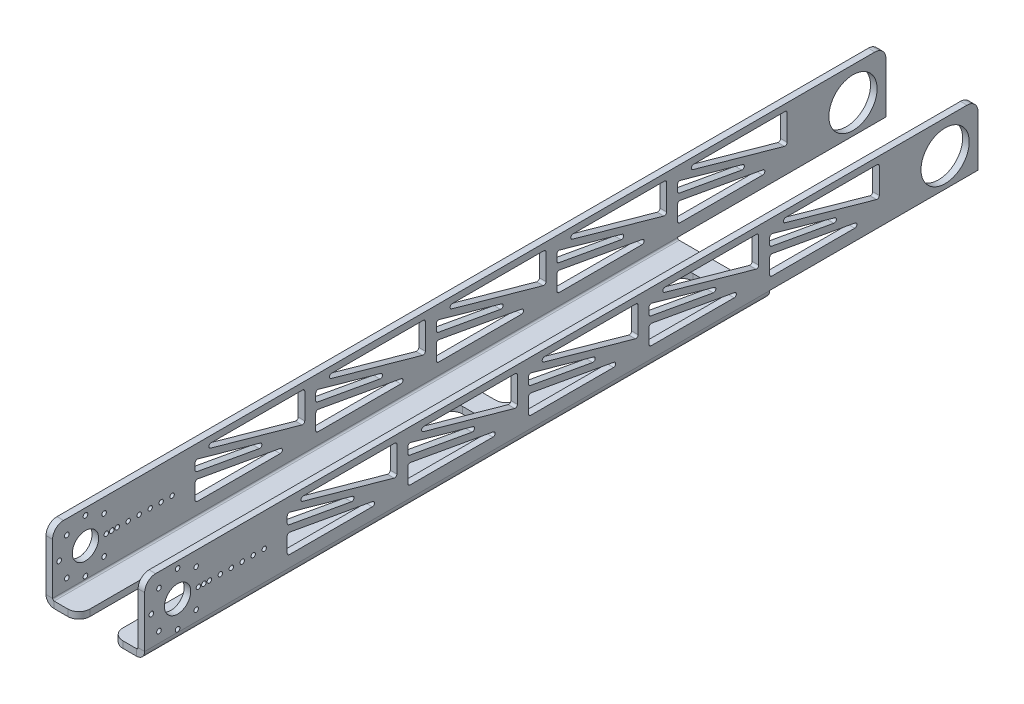
SolidWorks part; units mm, degrees
material "6061 Alloy"
ref_plane "Front Plane" through (0, 0, 0) normal (0, 0, 1) x (1, 0, 0)
ref_plane "Top Plane" through (0, 0, 0) normal (0, 1, 0) x (1, 0, 0)
ref_plane "Right Plane" through (0, 0, 0) normal (1, 0, 0) x (0, 0, -1)
sketch "Sketch1" plane through (0, 0, 0) normal (0, 1, 0) x (1, 0, 0)
  line L1 (-22.5, -190) -> (22.5, -190)
  line L2 (-22.5, -190) -> (-22.5, 190)
  line L3 (-22.5, 190) -> (22.5, 190)
  line L4 (22.5, -190) -> (22.5, 190)
  line L5 (0, 190) -> (0, -190) construction
  line L6 (-22.5, 0) -> (22.5, 0) construction
  point P0 (0, 0)
  dimension "D1" = 380
  dimension "D2" = 45
base flange "Base-Flange1" sketch "Sketch1" thickness 3 reverse thickness direction no parameters "D1"=0.7366
edge flange "Edge-Flange1" sketch "Sketch10" flange profiles "Sketch10", "Sketch11" flange angle 90 flange length 32 flange position material inside bend radius 0.7366 thickness 3 relief rectangular parameters "D6"=10, "D8"=1
sketch "Sketch10" plane through (-22.5, 0, 0) normal (-1, 0, 0) x (0, 0, 1)
  line L2 (-190, 0) -> (-190, 29)
  line L3 (-190, 29) -> (190, 29)
  line L4 (190, 29) -> (190, 0)
  line L7 (-190, 0) -> (190, 0) construction
  line L8 (-190, 0) -> (190, 0)
sketch "Sketch11" plane through (22.5, 0, 0) normal (1, 0, 0) x (0, 0, -1)
  line L2 (190, 0) -> (190, 29)
  line L3 (190, 29) -> (-190, 29)
  line L4 (-190, 29) -> (-190, 0)
  line L13 (-190, 0) -> (190, 0) construction
  line L14 (-190, 0) -> (190, 0)
bend "EdgeBend1" bend radius 0.7366 bend angle 90 parameters "D5"=1
bend "EdgeBend2" bend radius 0.7366 bend angle 90 parameters "D5"=2
sketch "Sketch12" plane through (0, 0, 0) normal (0, 1, 0) x (1, 0, 0)
  line L32 (7.5, -10) -> (-7.5, -10)
  line L33 (-7.5, -10) -> (-7.5, 85)
  line L34 (-7.5, 85) -> (7.5, 85)
  line L35 (7.5, -10) -> (7.5, 85)
  line L36 (7.5, -115) -> (-7.5, -115)
  line L37 (-7.5, -115) -> (-7.5, -20)
  line L38 (-7.5, -20) -> (7.5, -20)
  line L39 (7.5, -115) -> (7.5, -20)
  line L44 (-7.5, 85) -> (7.5, -10) construction
  point P6 (0, 37.5)
  dimension "D3" = 15
  dimension "D5" = 10
  dimension "D7" = 95
  dimension "D8" = 15
  dimension "D9" = 95
  dimension "D1" = 10
extrude "Cut-Extrude1" cut sketch "Sketch12" against normal through all both and the other way through all normal cut yes
pattern_linear "LPattern1" count 4 spacing 105 along (0, 0, 1) of "Cut-Extrude1"
sketch "Sketch14" plane through (0, 0, 0) normal (1, 0, 0) x (0, 0, -1)
  line L0 (175, 14) -> (-175, 14) construction
  line L1 (190, 0.7366) -> (190, 29) construction
  circle A2 centre (-165.5, 14) radius 1
  circle A7 centre (-175, 14) radius 6
  circle A14 centre (-160.5, 14) radius 1
  circle A15 centre (-155.5, 14) radius 1
  circle A16 centre (-150.5, 14) radius 1
  circle A17 centre (-145.5, 14) radius 1
  circle A18 centre (-140.5, 14) radius 1
  circle A19 centre (-135.5, 14) radius 1
  circle A20 centre (175, 14) radius 12.5 construction
  circle A21 centre (175, 14) radius 11
  circle A22 centre (-175, 14) radius 12 construction
  circle A23 centre (-175, 26) radius 1.05
  circle A24 centre (-166.5147, 22.4853) radius 1.05
  circle A25 centre (-163, 14) radius 1.05
  circle A26 centre (-166.5147, 5.5147) radius 1.05
  circle A27 centre (-175, 2) radius 1.05
  circle A28 centre (-183.4853, 5.5147) radius 1.05
  circle A29 centre (-187, 14) radius 1.05
  circle A30 centre (-183.4853, 22.4853) radius 1.05
  point P6 (0, 14)
  dimension "D1" = 25
  dimension "D3" = 12
  dimension "D4" = 2
  dimension "D6" = 22
  dimension "D8" = 7
  dimension "D11" = 24
  dimension "D12" = 2.1
  dimension "D2" = 350
  dimension "D5" = 9.5
  dimension "D7" = 14
  dimension "D9" = 5
  dimension "D10" = 15
  dimension "D13" = 8
extrude "Cut-Extrude2" cut sketch "Sketch14" against normal through all both and the other way through all normal cut yes
fillet "Fillet1" radius 5 16 edges at (-21, 29, 190) (21, 29, 190) (21, 29, -190) (-21, 29, -190) (7.5, -1.5, 115) (-7.5, -1.5, 115) (-7.5, -1.5, 20) (7.5, -1.5, 20) (7.5, -1.5, 10) (-7.5, -1.5, 10) (7.5, -1.5, -85) (-7.5, -1.5, -85) (-7.5, -1.5, 190) (7.5, -1.5, 190) (7.5, -1.5, 125) (-7.5, -1.5, 125)
sketch "Sketch16" plane through (0, 0, 0) normal (1, 0, 0) x (0, 0, -1)
  line L0 (-125, 26) -> (-75, 26) construction
  line L1 (-125, 26) -> (-125, 6) construction
  line L2 (-125, 6) -> (-75, 6) construction
  line L3 (-75, 26) -> (-75, 6) construction
  line L4 (-100, 6) -> (-100, 26) construction
  line L5 (-125, 16) -> (-75, 16) construction
  line L6 (-125, 26) -> (-75, 12)
  line L7 (-75, 6) -> (-125, 15)
  line L8 (-125, 26) -> (-75, 26)
  line L9 (-75, 26) -> (-75, 12)
  line L10 (-125, 15) -> (-125, 6)
  line L11 (-125, 6) -> (-75, 6)
  line L12 (-125, 23) -> (-125, 18)
  line L13 (-125, 18) -> (-75, 9)
  line L14 (-75, 9) -> (-125, 23)
  point P0 (0, 16)
  point P1 (-100, 16)
  dimension "D1" = 50
  dimension "D2" = 14
  dimension "D4" = 9
  dimension "D5" = 3
  dimension "D7" = 100
  dimension "D8" = 16
  dimension "D9" = 20
extrude "Cut-Extrude3" cut sketch "Sketch16" against normal through all both and the other way through all normal cut yes
pattern_linear "LPattern2" count 5 spacing 55 along (0, 0, -1) of "Cut-Extrude3"
fillet "Fillet2" radius 1 90 edges at (-21, 12, 75) (-21, 26, 125) (-21, 26, 75) (-21, 23, 125) (-21, 9, 75) (-21, 15, 70) (-21, 6, 20) (-21, 6, 70) (-21, 15, 15) (-21, 6, -35) (-21, 6, 15) (-21, 15, -40) (-21, 6, -90) (-21, 6, -40) (-21, 15, -95) (-21, 6, -145) (-21, 6, -95) (-21, 12, 20) (-21, 26, 70) (-21, 26, 20) (-21, 12, -35) (-21, 26, 15) (-21, 26, -35) (-21, 12, -90) (-21, 26, -40) (-21, 26, -90) (-21, 12, -145) (-21, 26, -95) (-21, 26, -145) (-21, 18, 70) (-21, 23, 70) (-21, 9, 20) (-21, 18, 15) (-21, 23, 15) (-21, 9, -35) (-21, 18, -40) (-21, 23, -40) (-21, 9, -90) (-21, 18, -95) (-21, 23, -95) (-21, 9, -145) (-21, 18, 125) (-21, 15, 125) (-21, 6, 75) (-21, 6, 125) (21, 12, 75) (21, 26, 125) (21, 26, 75) (21, 18, 125) (21, 23, 125) (21, 9, 75) (21, 15, 125) (21, 6, 75) (21, 26, 20) (21, 12, 20) (21, 26, 70) (21, 26, -35) (21, 12, -35) (21, 26, 15) (21, 26, -90) (21, 12, -90) (21, 26, -40) (21, 26, -145) (21, 12, -145) (21, 26, -95) (21, 9, 20) (21, 18, 70) (21, 23, 70) (21, 9, -35) (21, 18, 15) (21, 23, 15) (21, 9, -90) (21, 18, -40) (21, 23, -40) (21, 9, -145) (21, 18, -95) (21, 23, -95) (21, 6, 70) (21, 15, 70) (21, 6, 20) (21, 6, 15) (21, 15, 15) (21, 6, -35) (21, 6, -40) (21, 15, -40) (21, 6, -90) (21, 6, -95) (21, 15, -95) (21, 6, -145) (21, 6, 125)
sketch "Sketch19" plane through (0, 0, 0) normal (1, 0, 0) x (0, 0, -1)
  line L0 (190, 0.7366) -> (190, 24) construction
  line L1 (190, 0.8) -> (95, 0.8)
  line L2 (190, 0.8) -> (190, -3)
  line L3 (190, -3) -> (95, -3)
  line L4 (95, 0.8) -> (95, -3)
  line L5 (190, 0.8) -> (95, -3) construction
  line L6 (190, -3) -> (95, 0.8) construction
  line L7 (190, -3) -> (-190, -3) construction
  point P4 (142.5, -1.1)
  dimension "D1" = 95
  dimension "D2" = 3.8
extrude "Cut-Extrude6" cut sketch "Sketch19" against normal through all both and the other way through all
sketch "Bend-Lines1" plane through (0, 0, 0) normal (0, 1, 0) x (1, 0, 0)
sketch "Bounding-Box1" plane through (0, 0, 0) normal (0, 1, 0) x (1, 0, 0)
equation "\"D8@Sketch12\"=\"D3@Sketch12\""
equation "\"D9@Sketch12\"=\"D7@Sketch12\""
